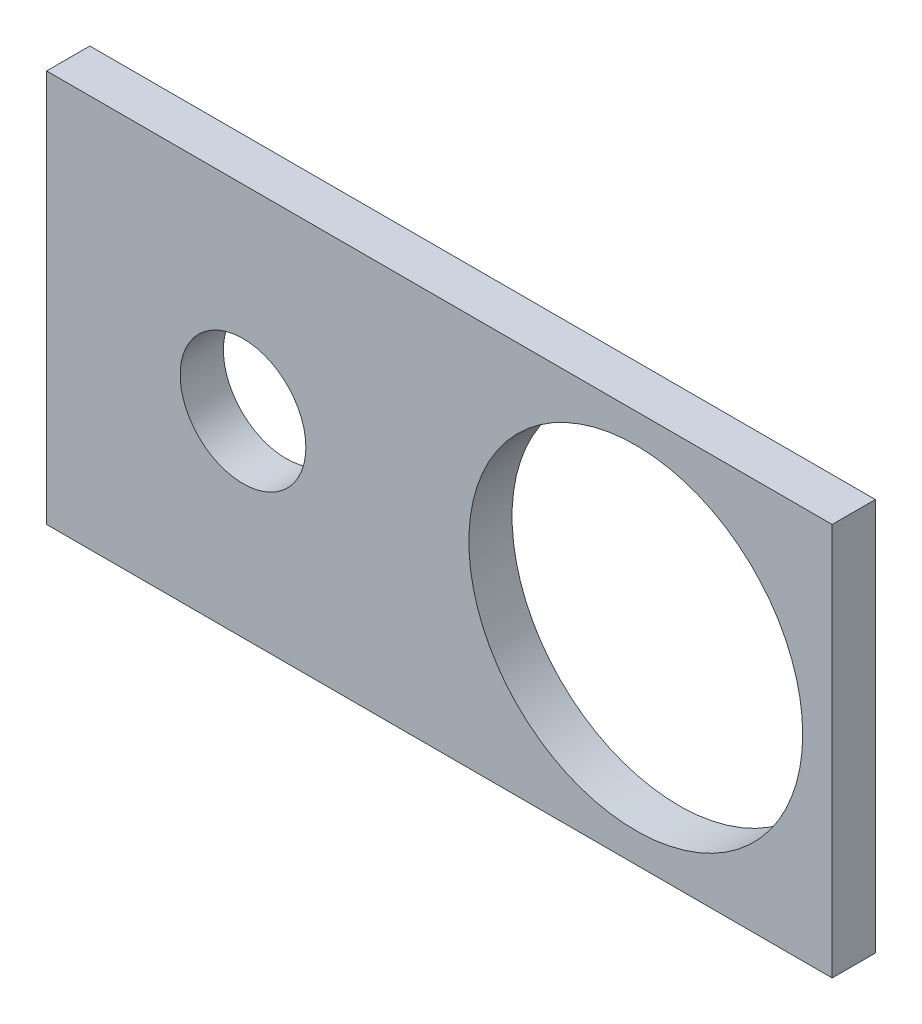
SolidWorks part; units mm, degrees
material "Delrin 2700 NC010, copolymère d'acétal à faible viscosité (SS)"
ref_plane "Plan de face" through (0, 0, 0) normal (0, 0, 1) x (1, 0, 0)
ref_plane "Plan de dessus" through (0, 0, 0) normal (0, 1, 0) x (1, 0, 0)
ref_plane "Plan de droite" through (0, 0, 0) normal (1, 0, 0) x (0, 0, -1)
sketch "Esquisse1" plane through (0, 0, 0) normal (0, 0, 1) x (1, 0, 0)
  line L0 (0, 0) -> (-100, 0) construction
  line L2 (50, 50) -> (-150, 50)
  line L3 (50, 50) -> (50, -50)
  line L4 (50, -50) -> (-150, -50)
  line L5 (-150, 50) -> (-150, -50)
  line L6 (50, 50) -> (-150, -50) construction
  line L7 (50, -50) -> (-150, 50) construction
  circle A0 centre (0, 0) radius 42.5
  circle A1 centre (-100, 0) radius 16
  point P5 (-50, 0)
  dimension "D1" = 85
  dimension "D2" = 32
  dimension "D3" = 100
  dimension "D4" = 100
  dimension "D5" = 200
extrude "Boss.-Extru.1" add sketch "Esquisse1" along normal blind 11
